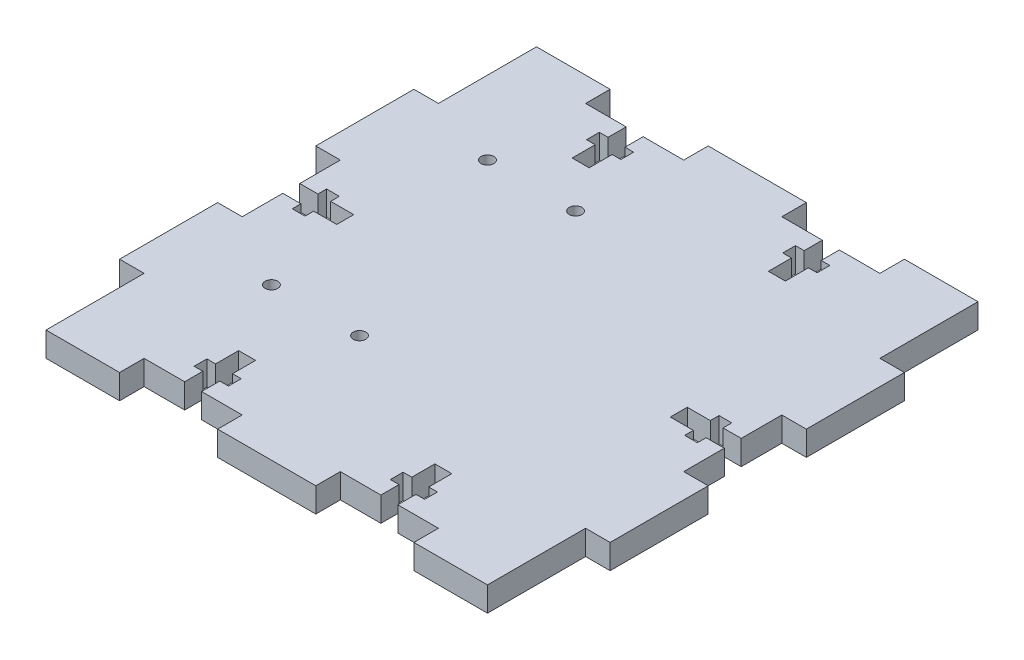
SolidWorks part; units mm, degrees
ref_plane "Front Plane" through (0, 0, 0) normal (0, 0, 1) x (1, 0, 0)
ref_plane "Top Plane" through (0, 0, 0) normal (0, 1, 0) x (1, 0, 0)
ref_plane "Right Plane" through (0, 0, 0) normal (1, 0, 0) x (0, 0, -1)
sketch "Sketch1" plane through (0, 0, 0) normal (0, 1, 0) x (1, 0, 0)
  line L1 (0, 0) -> (127, 0)
  line L2 (0, 0) -> (0, 127)
  line L3 (0, 127) -> (127, 127)
  line L4 (127, 0) -> (127, 127)
  dimension "D1" = 127
  dimension "D2" = 127
extrude "Boss-Extrude1" add sketch "Sketch1" along normal blind 6.35
sketch "Sketch2" plane through (0, 6.35, 0) normal (0, 1, 0) x (1, 0, 0)
  line L1 (0, 127) -> (6.35, 127)
  line L2 (0, 127) -> (0, 101.6)
  line L3 (0, 101.6) -> (6.35, 101.6)
  line L4 (6.35, 127) -> (6.35, 101.6)
  dimension "D1" = 25.4
  dimension "D2" = 6.35
extrude "Cut-Extrude1" cut sketch "Sketch2" against normal blind 6.35
pattern_linear "LPattern1" count 3 spacing 50.8 along (0, 0, 1) count 2 spacing 120.65 along (1, 0, 0) of "Cut-Extrude1"
sketch "Sketch3" plane through (0, 6.35, 0) normal (0, 1, 0) x (1, 0, 0)
  line L0 (6.35, 0) -> (120.65, 0) construction
  line L1 (25.4, 0) -> (50.8, 0)
  line L2 (25.4, 0) -> (25.4, 6.35)
  line L3 (25.4, 6.35) -> (50.8, 6.35)
  line L4 (50.8, 0) -> (50.8, 6.35)
  line L5 (0, 50.8) -> (0, 25.4) construction
  dimension "D1" = 25.4
  dimension "D2" = 6.35
  dimension "D3" = 25.4
extrude "Cut-Extrude2" cut sketch "Sketch3" against normal blind 6.35
pattern_linear "LPattern2" count 2 spacing 50.8 along (1, 0, 0) count 2 spacing 120.65 along (0, 0, -1) of "Cut-Extrude2"
ref_plane "Plane1" through (0, 0, -63.5) normal (0, 0, 1) x (1, 0, 0)
ref_plane "Plane2" through (63.5, 0, 0) normal (1, 0, 0) x (0, 0, -1)
sketch "Sketch4" plane through (0, 6.35, 0) normal (0, 1, 0) x (1, 0, 0)
  line L0 (120.65, 76.2) -> (120.65, 50.8) construction
  line L1 (120.65, 65.6971) -> (106.68, 65.6971)
  line L2 (120.65, 65.6971) -> (120.65, 61.3029)
  line L3 (120.65, 61.3029) -> (106.68, 61.3029)
  line L4 (106.68, 65.6971) -> (106.68, 61.3029)
  line L5 (127, 76.2) -> (120.65, 76.2) construction
  line L7 (112.649, 67.945) -> (115.951, 67.945)
  line L8 (112.649, 67.945) -> (112.649, 59.055)
  line L9 (112.649, 59.055) -> (115.951, 59.055)
  line L10 (115.951, 67.945) -> (115.951, 59.055)
  point P6 (120.65, 63.5)
  point P13 (114.3, 59.055)
  point P14 (115.951, 63.5)
  dimension "D1" = 13.97
  dimension "D2" = 4.3942
  dimension "D3" = 12.7
  dimension "D4" = 3.302
  dimension "D5" = 6.35
  dimension "D6" = 8.89
  dimension "D7" = 12.7
extrude "Cut-Extrude3" cut sketch "Sketch4" against normal blind 8.89 contours L1 L4 L3 L2 | L7 L10 L9 L8
mirror "Mirror1" about plane through (63.5, 0, 0) normal (1, 0, 0) of "Cut-Extrude3"
sketch "Sketch5" plane through (0, 6.35, 0) normal (0, 1, 0) x (1, 0, 0)
  line L0 (50.8, 6.35) -> (25.4, 6.35) construction
  line L1 (35.9029, 6.35) -> (40.2971, 6.35)
  line L2 (35.9029, 6.35) -> (35.9029, 20.32)
  line L3 (35.9029, 20.32) -> (40.2971, 20.32)
  line L4 (40.2971, 6.35) -> (40.2971, 20.32)
  line L5 (50.8, 0) -> (50.8, 6.35) construction
  line L6 (33.655, 14.351) -> (42.545, 14.351)
  line L7 (33.655, 14.351) -> (33.655, 11.049)
  line L8 (33.655, 11.049) -> (42.545, 11.049)
  line L9 (42.545, 14.351) -> (42.545, 11.049)
  point P6 (38.1, 20.32)
  point P12 (38.1, 11.049)
  point P15 (42.545, 12.7)
  dimension "D1" = 13.97
  dimension "D2" = 4.3942
  dimension "D3" = 12.7
  dimension "D4" = 3.302
  dimension "D5" = 8.89
  dimension "D6" = 12.7
  dimension "D7" = 6.35
extrude "Cut-Extrude4" cut sketch "Sketch5" against normal blind 30.48 contours L3 L4 L1 L2 | L7 L8 L9 L6
mirror "Mirror2" about plane through (63.5, 0, 0) normal (1, 0, 0) of "Cut-Extrude4"
mirror "Mirror3" about plane through (0, 0, -63.5) normal (0, 0, 1) of "Mirror2"
sketch "Sketch10" plane through (0, 6.35, 0) normal (0, 1, 0) x (1, 0, 0)
  line L0 (0, 101.6) -> (0, 76.2) construction
  line L1 (25.4, 95.25) -> (48.2092, 95.25)
  line L2 (25.4, 95.25) -> (25.4, 39.3192)
  line L3 (25.4, 39.3192) -> (48.2092, 39.3192)
  line L4 (48.2092, 95.25) -> (48.2092, 39.3192)
  line L5 (127, 120.65) -> (152.4, 120.65) construction
  point P6 (0, 88.9)
  dimension "D1" = 22.8092
  dimension "D2" = 55.9308
  dimension "D4" = 25.4
  dimension "D5" = 25.4
hole_wizard "#4 Clearance Hole2" positions "Sketch12" profile "Sketch11" hole size "#4" standard "ANSI Inch"
sketch "Sketch12" plane through (0, 6.35, 0) normal (0, 1, 0) x (1, 0, 0)
  point P0 (25.4, 95.25)
  point P3 (48.2092, 95.25)
  point P6 (48.2092, 39.3192)
  point P9 (25.4, 39.3192)
sketch "Sketch11" plane through (25.4, 6.35, -95.25) normal (1, 0, 0) x (0, 0, 1)
  line L0 (0, 0) -> (0, 11.1406)
  line L1 (0, 11.1406) -> (1.6319, 10.16)
  line L2 (1.6319, 10.16) -> (1.6319, 0)
  line L5 (1.6319, 0) -> (0, 0)
  line L10 (0, 11.1406) -> (-1.6319, 10.16) construction
  line L11 (0, -6.35) -> (0, 107.95) construction
  dimension "Hole Dia." = 3.2639
  dimension "Hole Depth" = 10.16
  dimension "Drill Angle" = 118
